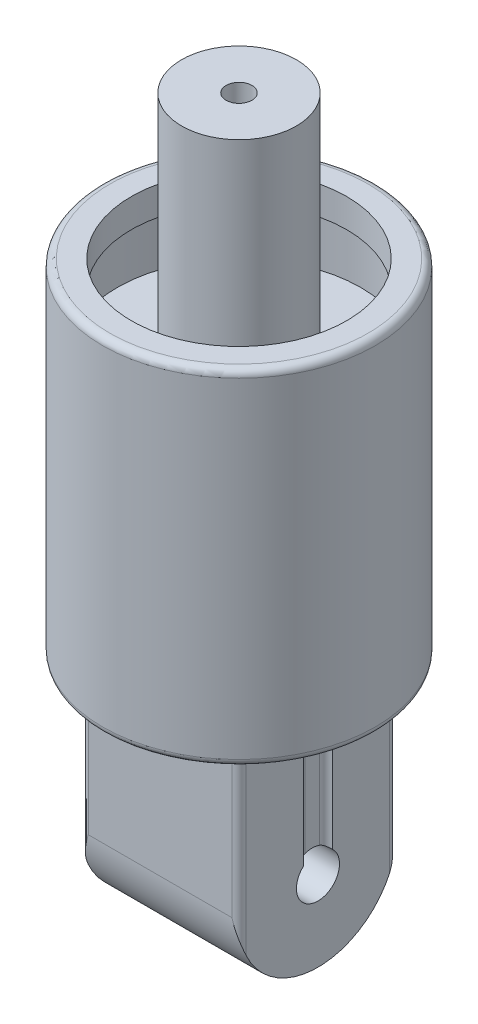
SolidWorks part; units mm, degrees
ref_plane "Plan de face" through (0, 0, 0) normal (0, 0, 1) x (1, 0, 0)
ref_plane "Plan de dessus" through (0, 0, 0) normal (0, 1, 0) x (1, 0, 0)
ref_plane "Plan de droite" through (0, 0, 0) normal (1, 0, 0) x (0, 0, -1)
sketch "Esquisse1" plane through (0, 0, 0) normal (0, 0, 1) x (1, 0, 0)
  line L0 (0, 0) -> (0, 12) construction
  line L1 (0, 0) -> (4.75, 0) construction
  line L2 (4.75, 0) -> (4.75, 12) construction
  line L3 (4.75, 12) -> (0, 12) construction
  line L4 (1, 12) -> (1, 0) construction
  line L5 (2, 9) -> (2, 17)
  line L6 (4.5, 12) -> (3.75, 12)
  line L7 (4.75, 11.75) -> (4.75, 0.25)
  line L8 (4.5, 0) -> (1, 0)
  line L9 (3.75, 12) -> (3.75, 11)
  line L10 (3.75, 11) -> (4.25, 11)
  line L11 (4.25, 11) -> (4.25, 9)
  line L12 (4.25, 9) -> (2, 9)
  line L13 (2, 9) -> (2, 12) construction
  line L14 (2, 17) -> (0.45, 17)
  line L15 (0.45, 17) -> (0.45, 12)
  line L16 (0.45, 12) -> (1, 12)
  line L17 (1, 12) -> (1, 0)
  arc A0 (4.75, 0.25) -> (4.5, 0) centre (4.5, 0.25) cw
  arc A1 (4.75, 11.75) -> (4.5, 12) centre (4.5, 11.75) ccw
  dimension "D9" = 0.25
  dimension "D1" = 12
  dimension "D2" = 9.5
  dimension "D3" = 2
  dimension "D4" = 1
  dimension "D5" = 1
  dimension "D6" = 0.5
  dimension "D7" = 2
  dimension "D8" = 1
  dimension "D10" = 5
  dimension "D11" = 0.9
revolve "Révolution1" add sketch "Esquisse1" angle 360 about L0
sketch "Esquisse4" plane through (0, 0, 0) normal (0, -1, 0) x (1, 0, 0)
  line L1 (-2.5, -2.75) -> (2.5, -2.75)
  line L2 (-2.75, -2.5) -> (-2.75, 2.5)
  line L3 (-2.5, 2.75) -> (2.5, 2.75)
  line L4 (2.75, -2.5) -> (2.75, 2.5)
  line L5 (-2.75, -2.75) -> (2.75, 2.75) construction
  line L6 (-2.75, 2.75) -> (2.75, -2.75) construction
  circle A0 centre (0, 0) radius 1 construction
  circle A1 centre (0, 0) radius 1
  arc A2 (-2.5, -2.75) -> (-2.75, -2.5) centre (-2.5, -2.5) cw
  arc A3 (2.75, -2.5) -> (2.5, -2.75) centre (2.5, -2.5) cw
  arc A4 (2.75, 2.5) -> (2.5, 2.75) centre (2.5, 2.5) ccw
  arc A5 (-2.75, 2.5) -> (-2.5, 2.75) centre (-2.5, 2.5) cw
  point P0 (0, 0)
  dimension "D2" = 0.25
  dimension "D1" = 5.5
extrude "Boss.-Extru.2" add sketch "Esquisse4" along normal blind 8
sketch "Esquisse5" plane through (2.75, 0, 0) normal (1, 0, 0) x (0, 0, -1)
  line L0 (-2.75, -8) -> (-2.75, 0) construction
  line L1 (2.75, -8) -> (2.75, 0) construction
  line L2 (2.75, -5.25) -> (-2.75, -5.25) construction
  line L3 (2.5, -8) -> (-2.5, -8) construction
  line L4 (2.75, -5.25) -> (2.75, -8)
  line L5 (2.75, -8) -> (-2.75, -8)
  line L6 (-2.75, -8) -> (-2.75, -5.25)
  arc A0 (-2.75, -5.25) -> (2.75, -5.25) centre (0, -5.25) ccw
  circle A1 centre (0, -5.25) radius 0.75
  line M2 (-2.5, 0) -> (-2.5, -8)
  line M3 (-2.5, -8) -> (2.5, -8)
  line M4 (2.5, -8) -> (2.5, 0)
  dimension "D1" = 1.5
extrude "Enlèv. mat.-Extru.1" cut sketch "Esquisse5" against normal through all contours A0 M2 M3 | A0 L5 M4 | A0 L6 L5 M2 | A0 L5 L4 M4 | L2 A1 | A1 L2 region at (2.75, -6.9922, -2.6346) region at (2.75, -7.5583, -1.917) region at (2.75, -5.5683, 0) region at (2.75, -4.9317, 0) region at (2.75, -7.5583, 1.917) region at (2.75, -6.9922, 2.6346)
sketch "Esquisse6" plane through (0, 0, -2.75) normal (0, 0, 1) x (1, 0, 0)
  line L0 (-1, -8) -> (-1, -2.5)
  line L1 (-1, -2.5) -> (1, -2.5)
  line L2 (1, -2.5) -> (1, -8)
  line L3 (1, -8) -> (-1, -8)
  dimension "D1" = 2
  dimension "D2" = 2.5
extrude "Enlèv. mat.-Extru.2" cut sketch "Esquisse6" along normal up to next
fillet "Congé1" radius 0.25 6 edges at (-1, -3.875, -2.75) (-1, -7.1945, -1.9445) (-0.0866, -7.8132, 0.9962) (1, -7.1945, -1.9445) (1, -3.875, -2.75) (0, -2.5, -2.75)
sketch "Esquisse7" plane through (-2.75, 0, 0) normal (-1, 0, 0) x (0, 0, 1)
  line L0 (0, 0) -> (0, -4.5) construction
  line L1 (2.5, 0) -> (-2.5, 0) construction
  line L2 (-0.5, -4.691) -> (0.5, -4.691)
  line L3 (-0.5, -4.691) -> (-0.5, 0)
  line L4 (-0.5, 0) -> (0.5, 0)
  line L5 (0.5, -4.691) -> (0.5, 0)
  line L6 (-0.5, -4.691) -> (0.5, 0) construction
  line L7 (-0.5, 0) -> (0.5, -4.691) construction
  circle A0 centre (0, -5.25) radius 0.75 construction
  point P6 (0, -2.3455)
  point P11 (0, 0)
  point P12 (-0.5, 0)
  dimension "D1" = 1
extrude "Enlèv. mat.-Extru.3" cut sketch "Esquisse7" against normal blind 0.2
fillet "Congé2" radius 0.25 2 edges at (-2.55, -2.3455, 0.5) (-2.55, -2.3455, -0.5)
mirror "Symétrie1" about plane through (0, 0, 0) normal (1, 0, 0) of "Enlèv. mat.-Extru.3", "Congé2"
